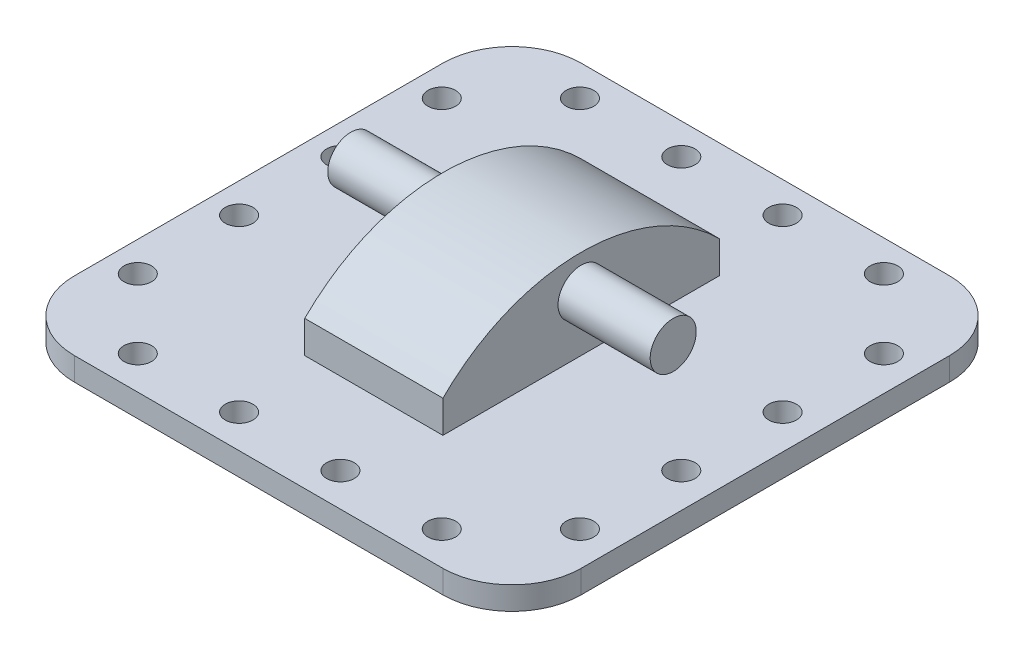
SolidWorks part; units mm, degrees
ref_plane "Front Plane" through (0, 0, 0) normal (0, 0, 1) x (1, 0, 0)
ref_plane "Top Plane" through (0, 0, 0) normal (0, 1, 0) x (1, 0, 0)
ref_plane "Right Plane" through (0, 0, 0) normal (1, 0, 0) x (0, 0, -1)
sketch "Sketch1" plane through (0, 0, 0) normal (0, 1, 0) x (1, 0, 0)
  line L1 (-55, -55) -> (55, -55)
  line L2 (-55, -55) -> (-55, 55)
  line L3 (-55, 55) -> (55, 55)
  line L4 (55, -55) -> (55, 55)
  line L5 (-55, -55) -> (55, 55) construction
  line L6 (-55, 55) -> (55, -55) construction
  point P0 (0, 0)
  dimension "D1" = 110
  dimension "D2" = 110
extrude "Boss-Extrude1" add sketch "Sketch1" along normal blind 5
fillet "Fillet2" radius 15 1 edges at (55, 2.5, -55) type face fillet first side face at (55, 2.5, 0) second side face at (0, 2.5, -55)
fillet "Fillet3" radius 15 1 edges at (-55, 2.5, -55) type face fillet first side face at (-7.5, 2.5, -55) second side face at (-55, 2.5, 0)
fillet "Fillet4" radius 15 1 edges at (-55, 2.5, 55) type face fillet first side face at (-55, 2.5, 7.5) second side face at (0, 2.5, 55)
fillet "Fillet5" radius 15 1 edges at (55, 2.5, 55) type face fillet first side face at (7.5, 2.5, 55) second side face at (55, 2.5, 7.5)
sketch "Sketch2" plane through (0, 5, 0) normal (0, 1, 0) x (1, 0, 0)
  line L1 (-15, -30) -> (15, -30)
  line L2 (-15, -30) -> (-15, 30)
  line L3 (-15, 30) -> (15, 30)
  line L4 (15, -30) -> (15, 30)
  line L5 (-15, -30) -> (15, 30) construction
  line L6 (-15, 30) -> (15, -30) construction
  point P0 (0, 0)
extrude "Boss-Extrude2" add sketch "Sketch2" along normal blind 24
sketch "Sketch4" plane through (15, 0, 0) normal (1, 0, 0) x (0, 0, -1)
  line L0 (-30, 17) -> (30, 17) construction
  line L1 (-30, 29) -> (-30, 5) construction
  line L2 (30, 29) -> (30, 5) construction
  line L3 (0, 17) -> (0, 29) construction
  line L4 (-30, 29) -> (30, 29) construction
  line L5 (0, 29) -> (0, 5) construction
  line L6 (-40, 5) -> (40, 5) construction
  circle A2 centre (0, 17) radius 5
extrude "Boss-Extrude3" add sketch "Sketch4" along normal blind 20 and the other way blind 50
fillet "Fillet6" radius 10 1 edges at (0, 29, 30)
fillet "Fillet7" radius 10 1 edges at (0, 29, -30)
sketch "Sketch5" plane through (0, 0, 0) normal (0, -1, 0) x (1, 0, 0)
  line L0 (54.498, -40.251) -> (54.498, 39.749)
  line L1 (39.498, 54.749) -> (-40.502, 54.749)
  line L2 (-55.502, 39.749) -> (-55.502, -40.251)
  line L3 (-40.502, -55.251) -> (39.498, -55.251)
  circle A0 centre (47.498, -11.251) radius 3
  circle A1 centre (47.498, 32.749) radius 3
  circle A2 centre (-48.502, 10.749) radius 3
  circle A3 centre (-48.502, -11.251) radius 3
  circle A4 centre (-48.502, -33.251) radius 3
  circle A5 centre (-33.502, -48.251) radius 3
  circle A6 centre (-11.502, -48.251) radius 3
  circle A7 centre (10.498, -48.251) radius 3
  circle A8 centre (32.498, -48.251) radius 3
  circle A9 centre (47.498, -33.251) radius 3
  circle A10 centre (47.498, 10.749) radius 3
  circle A11 centre (32.498, 47.749) radius 3
  circle A12 centre (10.498, 47.749) radius 3
  circle A13 centre (-11.502, 47.749) radius 3
  circle A14 centre (-33.502, 47.749) radius 3
  circle A15 centre (-48.502, 32.749) radius 3
  arc A16 (54.498, 39.749) -> (39.498, 54.749) centre (39.498, 39.749) ccw
  arc A17 (-40.502, 54.749) -> (-55.502, 39.749) centre (-40.502, 39.749) ccw
  arc A18 (-55.502, -40.251) -> (-40.502, -55.251) centre (-40.502, -40.251) ccw
  arc A19 (39.498, -55.251) -> (54.498, -40.251) centre (39.498, -40.251) ccw
extrude "Cut-Extrude2" cut sketch "Sketch5" against normal blind 10 contours A5 | A4 | A3 | A2 | A1 | A0 | A7 | A6 | A15 | A14 | A13 | A12 | A11 | A10 | A9 | A8
sketch "Sketch6" plane through (0, 5, 0) normal (0, 1, 0) x (1, 0, 0)
  line L1 (-15, 30) -> (15, 30)
  line L2 (-15, 30) -> (-15, -30)
  line L3 (-15, -30) -> (15, -30)
  line L4 (15, 30) -> (15, -30)
sketch "Sketch8" plane through (-15, 0, 0) normal (-1, 0, 0) x (0, 0, 1)
  line L0 (-30, 19) -> (-30, 5) construction
  line L1 (30, 19) -> (30, 5) construction
  line L2 (-20, 29) -> (20, 29) construction
  line L3 (-30, 19) -> (-30, 12)
  line L4 (30, 19) -> (30, 12)
  line L5 (-20, 29) -> (20, 29)
  arc A0 (-30, 12) -> (30, 12) centre (0, -18) cw
  arc A1 (-20, 29) -> (-30, 19) centre (-20, 19) ccw construction
  arc A2 (30, 19) -> (20, 29) centre (20, 19) ccw construction
  arc A3 (-20, 29) -> (-30, 19) centre (-20, 19) ccw
  arc A4 (30, 19) -> (20, 29) centre (20, 19) ccw
extrude "Cut-Extrude3" cut sketch "Sketch8" against normal blind 60
split "Split1" bodies to split 123 resulting bodies 124 125 split by face at (-48.502, 5, 29.749)
